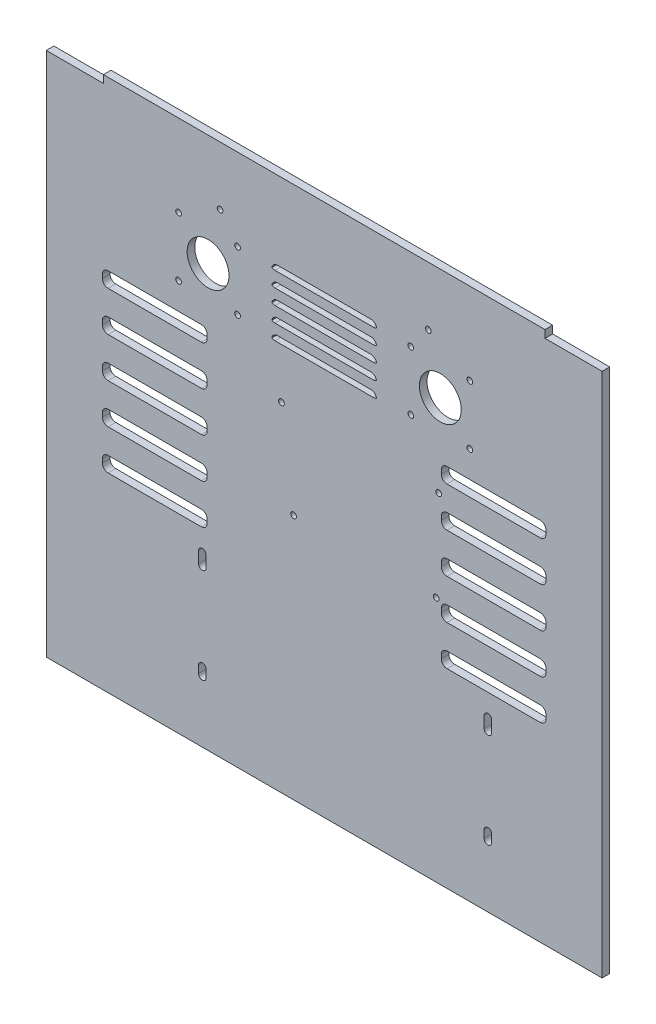
SolidWorks part; units mm, degrees
ref_plane "Front Plane" through (0, 0, 0) normal (0, 0, 1) x (1, 0, 0)
ref_plane "Top Plane" through (0, 0, 0) normal (0, 1, 0) x (1, 0, 0)
ref_plane "Right Plane" through (0, 0, 0) normal (1, 0, 0) x (0, 0, -1)
sketch "Sketch1" plane through (0, 0, 0) normal (0, 0, 1) x (1, 0, 0)
  line L0 (-45.5, 82.5) -> (-76.5, 82.5) construction
  line L1 (146, -123.5) -> (-146, -123.5)
  line L2 (146, -123.5) -> (146, 123.5)
  line L3 (146, 123.5) -> (-146, 123.5)
  line L4 (-146, -123.5) -> (-146, 123.5)
  line L5 (146, -123.5) -> (-146, 123.5) construction
  line L6 (146, 123.5) -> (-146, -123.5) construction
  line L7 (-45.5, 82.5) -> (-45.5, 113.5) construction
  line L8 (-45.5, 113.5) -> (-76.5, 113.5) construction
  line L9 (-76.5, 82.5) -> (-76.5, 113.5) construction
  line L10 (-45.5, 82.5) -> (-76.5, 113.5) construction
  line L11 (-45.5, 113.5) -> (-76.5, 82.5) construction
  line L12 (0, 123.5) -> (0, -133.2191) construction
  line L13 (45.5, 113.5) -> (76.5, 82.5) construction
  line L14 (45.5, 82.5) -> (76.5, 113.5) construction
  line L15 (76.5, 82.5) -> (76.5, 113.5) construction
  line L16 (45.5, 113.5) -> (76.5, 113.5) construction
  line L17 (45.5, 82.5) -> (45.5, 113.5) construction
  line L18 (45.5, 82.5) -> (76.5, 82.5) construction
  line L19 (-175.5662, 125.75) -> (218.0802, 125.75) construction
  line L20 (-146, 123.5) -> (146, 123.5)
  line L21 (-146, 123.5) -> (-146, 156.5)
  line L22 (-146, 156.5) -> (146, 156.5)
  line L23 (146, 123.5) -> (146, 156.5)
  line L24 (0, 156.5) -> (0, 123.5) construction
  line L25 (-146, 140) -> (146, 140) construction
  line L26 (146, 154.5) -> (116, 154.5) construction
  line L27 (-146, 156.5) -> (-116, 156.5)
  line L28 (-146, 156.5) -> (-146, 152.5)
  line L29 (-146, 152.5) -> (-116, 152.5)
  line L30 (-116, 156.5) -> (-116, 152.5)
  line L31 (-131, 152.5) -> (-131, 156.5) construction
  line L32 (-146, 154.5) -> (-116, 154.5) construction
  line L33 (131, 152.5) -> (131, 156.5) construction
  line L34 (116, 156.5) -> (116, 152.5)
  line L35 (146, 152.5) -> (116, 152.5)
  line L36 (146, 156.5) -> (146, 152.5)
  line L37 (146, 156.5) -> (116, 156.5)
  line L38 (-64, -41) -> (-64, -35.0783) construction
  line L39 (-66, -41) -> (-66, -35.0783)
  line L40 (-62, -41) -> (-62, -35.0783)
  line L41 (-64, -91) -> (-64, -87.0783) construction
  line L42 (-66, -91) -> (-66, -87.0783)
  line L43 (-62, -91) -> (-62, -87.0783)
  line L44 (86, -41) -> (86, -35.0783) construction
  line L45 (84, -41) -> (84, -35.0783)
  line L46 (88, -41) -> (88, -35.0783)
  line L47 (86, -91) -> (86, -87.0783) construction
  line L48 (84, -91) -> (84, -87.0783)
  line L49 (88, -91) -> (88, -87.0783)
  line L50 (-116.5, 64.5) -> (-61.5, 64.5) construction
  line L51 (113.5, 68.5) -> (64.5, 68.5)
  line L52 (116.5, 65.5) -> (116.5, 63.5)
  line L53 (113.5, 60.5) -> (64.5, 60.5)
  line L54 (61.5, 65.5) -> (61.5, 63.5)
  line L55 (89, 60.5) -> (89, 68.5) construction
  line L56 (116.5, 64.5) -> (61.5, 64.5) construction
  line L57 (-89, 60.5) -> (-89, 68.5) construction
  line L58 (-61.5, 65.5) -> (-61.5, 63.5)
  line L59 (-113.5, 60.5) -> (-64.5, 60.5)
  line L60 (-116.5, 65.5) -> (-116.5, 63.5)
  line L61 (-113.5, 68.5) -> (-64.5, 68.5)
  line L62 (113.5, 47.5) -> (64.5, 47.5)
  line L63 (116.5, 44.5) -> (116.5, 42.5)
  line L64 (113.5, 39.5) -> (64.5, 39.5)
  line L65 (61.5, 44.5) -> (61.5, 42.5)
  line L66 (-61.5, 44.5) -> (-61.5, 42.5)
  line L67 (-113.5, 39.5) -> (-64.5, 39.5)
  line L68 (-116.5, 44.5) -> (-116.5, 42.5)
  line L69 (-113.5, 47.5) -> (-64.5, 47.5)
  line L70 (-116.5, 43.5) -> (-61.5, 43.5) construction
  line L71 (89, 39.5) -> (89, 47.5) construction
  line L72 (116.5, 43.5) -> (61.5, 43.5) construction
  line L73 (-89, 39.5) -> (-89, 47.5) construction
  line L74 (113.5, 26.5) -> (64.5, 26.5)
  line L75 (116.5, 23.5) -> (116.5, 21.5)
  line L76 (113.5, 18.5) -> (64.5, 18.5)
  line L77 (61.5, 23.5) -> (61.5, 21.5)
  line L78 (-61.5, 23.5) -> (-61.5, 21.5)
  line L79 (-113.5, 18.5) -> (-64.5, 18.5)
  line L80 (-116.5, 23.5) -> (-116.5, 21.5)
  line L81 (-113.5, 26.5) -> (-64.5, 26.5)
  line L82 (-116.5, 22.5) -> (-61.5, 22.5) construction
  line L83 (89, 18.5) -> (89, 26.5) construction
  line L84 (116.5, 22.5) -> (61.5, 22.5) construction
  line L85 (-89, 18.5) -> (-89, 26.5) construction
  line L86 (113.5, 5.5) -> (64.5, 5.5)
  line L87 (116.5, 2.5) -> (116.5, 0.5)
  line L88 (113.5, -2.5) -> (64.5, -2.5)
  line L89 (61.5, 2.5) -> (61.5, 0.5)
  line L90 (-61.5, 2.5) -> (-61.5, 0.5)
  line L91 (-113.5, -2.5) -> (-64.5, -2.5)
  line L92 (-116.5, 2.5) -> (-116.5, 0.5)
  line L93 (-113.5, 5.5) -> (-64.5, 5.5)
  line L94 (-116.5, 1.5) -> (-61.5, 1.5) construction
  line L95 (89, -2.5) -> (89, 5.5) construction
  line L96 (116.5, 1.5) -> (61.5, 1.5) construction
  line L97 (-89, -2.5) -> (-89, 5.5) construction
  line L98 (113.5, -15.5) -> (64.5, -15.5)
  line L99 (116.5, -18.5) -> (116.5, -20.5)
  line L100 (113.5, -23.5) -> (64.5, -23.5)
  line L101 (61.5, -18.5) -> (61.5, -20.5)
  line L102 (-61.5, -18.5) -> (-61.5, -20.5)
  line L103 (-113.5, -23.5) -> (-64.5, -23.5)
  line L104 (-116.5, -18.5) -> (-116.5, -20.5)
  line L105 (-113.5, -15.5) -> (-64.5, -15.5)
  line L106 (-116.5, -19.5) -> (-61.5, -19.5) construction
  line L107 (89, -23.5) -> (89, -15.5) construction
  line L108 (116.5, -19.5) -> (61.5, -19.5) construction
  line L109 (-89, -23.5) -> (-89, -15.5) construction
  line L110 (-24.542, 107.5) -> (24.542, 107.5)
  line L111 (-24.542, 115.5) -> (24.542, 115.5)
  line L112 (-25.8417, 104.5) -> (25.8417, 104.5)
  line L113 (-25.8417, 112.5) -> (25.8417, 112.5)
  line L114 (0, 104.5) -> (0, 107.5) construction
  line L115 (0, 112.5) -> (0, 115.5) construction
  line L116 (-27.5, 113) -> (27.5, 113) construction
  line L117 (-27.5, 105) -> (27.5, 105) construction
  line L118 (-24.542, 99.5) -> (24.542, 99.5)
  line L119 (-25.8417, 96.5) -> (25.8417, 96.5)
  line L120 (0, 96.5) -> (0, 99.5) construction
  line L121 (-27.5, 97) -> (27.5, 97) construction
  line L122 (-24.542, 91.5) -> (24.542, 91.5)
  line L123 (-25.8417, 88.5) -> (25.8417, 88.5)
  line L124 (0, 88.5) -> (0, 91.5) construction
  line L125 (-27.5, 89) -> (27.5, 89) construction
  line L126 (-24.542, 83.5) -> (24.542, 83.5)
  line L127 (-25.8417, 80.5) -> (25.8417, 80.5)
  line L128 (0, 80.5) -> (0, 83.5) construction
  line L129 (-27.5, 81) -> (27.5, 81) construction
  circle A0 centre (-76.5, 113.5) radius 1.5
  circle A1 centre (-45.5, 113.5) radius 1.5
  circle A2 centre (76.5, 82.5) radius 1.5
  circle A3 centre (-61, 98) radius 11
  circle A4 centre (-45.5, 82.5) radius 1.5
  circle A5 centre (-76.5, 82.5) radius 1.5
  circle A6 centre (45.5, 82.5) radius 1.5
  circle A7 centre (61, 98) radius 11
  circle A8 centre (45.5, 113.5) radius 1.5
  circle A9 centre (76.5, 113.5) radius 1.5
  circle A10 centre (86, -41) radius 2 construction
  circle A11 centre (86, -91) radius 2 construction
  circle A12 centre (-64, -41) radius 2 construction
  circle A13 centre (-64, -91) radius 2 construction
  circle A14 centre (60.1213, 54.1951) radius 1.5
  circle A15 centre (-54.7, 125.75) radius 1.5
  circle A16 centre (-16.0787, 5.9351) radius 1.5
  circle A17 centre (58.8513, 5.9351) radius 1.5
  circle A18 centre (-22.4287, 54.1951) radius 1.5
  circle A19 centre (54.7, 125.75) radius 1.5
  arc A20 (-66, -41) -> (-62, -41) centre (-64, -41) ccw
  arc A21 (-62, -35.0783) -> (-66, -35.0783) centre (-64, -35.0783) ccw
  arc A22 (84, -41) -> (88, -41) centre (86, -41) ccw
  arc A23 (-66, -91) -> (-62, -91) centre (-64, -91) ccw
  arc A24 (-62, -87.0783) -> (-66, -87.0783) centre (-64, -87.0783) ccw
  arc A25 (88, -35.0783) -> (84, -35.0783) centre (86, -35.0783) ccw
  arc A26 (84, -91) -> (88, -91) centre (86, -91) ccw
  arc A27 (88, -87.0783) -> (84, -87.0783) centre (86, -87.0783) ccw
  arc A28 (64.5, 68.5) -> (61.5, 65.5) centre (64.5, 65.5) ccw
  arc A29 (64.5, 60.5) -> (61.5, 63.5) centre (64.5, 63.5) cw
  arc A30 (116.5, 63.5) -> (113.5, 60.5) centre (113.5, 63.5) cw
  arc A31 (113.5, 68.5) -> (116.5, 65.5) centre (113.5, 65.5) cw
  arc A32 (-113.5, 68.5) -> (-116.5, 65.5) centre (-113.5, 65.5) ccw
  arc A33 (-116.5, 63.5) -> (-113.5, 60.5) centre (-113.5, 63.5) ccw
  arc A34 (-64.5, 60.5) -> (-61.5, 63.5) centre (-64.5, 63.5) ccw
  arc A35 (-64.5, 68.5) -> (-61.5, 65.5) centre (-64.5, 65.5) cw
  arc A36 (64.5, 47.5) -> (61.5, 44.5) centre (64.5, 44.5) ccw
  arc A37 (64.5, 39.5) -> (61.5, 42.5) centre (64.5, 42.5) cw
  arc A38 (116.5, 42.5) -> (113.5, 39.5) centre (113.5, 42.5) cw
  arc A39 (113.5, 47.5) -> (116.5, 44.5) centre (113.5, 44.5) cw
  arc A40 (-113.5, 47.5) -> (-116.5, 44.5) centre (-113.5, 44.5) ccw
  arc A41 (-116.5, 42.5) -> (-113.5, 39.5) centre (-113.5, 42.5) ccw
  arc A42 (-64.5, 39.5) -> (-61.5, 42.5) centre (-64.5, 42.5) ccw
  arc A43 (-64.5, 47.5) -> (-61.5, 44.5) centre (-64.5, 44.5) cw
  arc A44 (64.5, 26.5) -> (61.5, 23.5) centre (64.5, 23.5) ccw
  arc A45 (64.5, 18.5) -> (61.5, 21.5) centre (64.5, 21.5) cw
  arc A46 (116.5, 21.5) -> (113.5, 18.5) centre (113.5, 21.5) cw
  arc A47 (113.5, 26.5) -> (116.5, 23.5) centre (113.5, 23.5) cw
  arc A48 (-113.5, 26.5) -> (-116.5, 23.5) centre (-113.5, 23.5) ccw
  arc A49 (-116.5, 21.5) -> (-113.5, 18.5) centre (-113.5, 21.5) ccw
  arc A50 (-64.5, 18.5) -> (-61.5, 21.5) centre (-64.5, 21.5) ccw
  arc A51 (-64.5, 26.5) -> (-61.5, 23.5) centre (-64.5, 23.5) cw
  arc A52 (64.5, 5.5) -> (61.5, 2.5) centre (64.5, 2.5) ccw
  arc A53 (64.5, -2.5) -> (61.5, 0.5) centre (64.5, 0.5) cw
  arc A54 (116.5, 0.5) -> (113.5, -2.5) centre (113.5, 0.5) cw
  arc A55 (113.5, 5.5) -> (116.5, 2.5) centre (113.5, 2.5) cw
  arc A56 (-113.5, 5.5) -> (-116.5, 2.5) centre (-113.5, 2.5) ccw
  arc A57 (-116.5, 0.5) -> (-113.5, -2.5) centre (-113.5, 0.5) ccw
  arc A58 (-64.5, -2.5) -> (-61.5, 0.5) centre (-64.5, 0.5) ccw
  arc A59 (-64.5, 5.5) -> (-61.5, 2.5) centre (-64.5, 2.5) cw
  arc A60 (64.5, -15.5) -> (61.5, -18.5) centre (64.5, -18.5) ccw
  arc A61 (64.5, -23.5) -> (61.5, -20.5) centre (64.5, -20.5) cw
  arc A62 (116.5, -20.5) -> (113.5, -23.5) centre (113.5, -20.5) cw
  arc A63 (113.5, -15.5) -> (116.5, -18.5) centre (113.5, -18.5) cw
  arc A64 (-113.5, -15.5) -> (-116.5, -18.5) centre (-113.5, -18.5) ccw
  arc A65 (-116.5, -20.5) -> (-113.5, -23.5) centre (-113.5, -20.5) ccw
  arc A66 (-64.5, -23.5) -> (-61.5, -20.5) centre (-64.5, -20.5) ccw
  arc A67 (-64.5, -15.5) -> (-61.5, -18.5) centre (-64.5, -18.5) cw
  arc A68 (25.8417, 112.5) -> (27.5, 113) centre (25.8417, 115.5) ccw
  arc A69 (-27.5, 113) -> (-25.8417, 112.5) centre (-25.8417, 115.5) ccw
  arc A70 (-24.542, 115.5) -> (-27.5, 113) centre (-24.542, 112.5) ccw
  arc A71 (24.542, 115.5) -> (27.5, 113) centre (24.542, 112.5) cw
  arc A72 (25.8417, 104.5) -> (27.5, 105) centre (25.8417, 107.5) ccw
  arc A73 (-27.5, 105) -> (-25.8417, 104.5) centre (-25.8417, 107.5) ccw
  arc A74 (-24.542, 107.5) -> (-27.5, 105) centre (-24.542, 104.5) ccw
  arc A75 (24.542, 107.5) -> (27.5, 105) centre (24.542, 104.5) cw
  arc A76 (25.8417, 96.5) -> (27.5, 97) centre (25.8417, 99.5) ccw
  arc A77 (-27.5, 97) -> (-25.8417, 96.5) centre (-25.8417, 99.5) ccw
  arc A78 (-24.542, 99.5) -> (-27.5, 97) centre (-24.542, 96.5) ccw
  arc A79 (24.542, 99.5) -> (27.5, 97) centre (24.542, 96.5) cw
  arc A80 (25.8417, 88.5) -> (27.5, 89) centre (25.8417, 91.5) ccw
  arc A81 (-27.5, 89) -> (-25.8417, 88.5) centre (-25.8417, 91.5) ccw
  arc A82 (-24.542, 91.5) -> (-27.5, 89) centre (-24.542, 88.5) ccw
  arc A83 (24.542, 91.5) -> (27.5, 89) centre (24.542, 88.5) cw
  arc A84 (25.8417, 80.5) -> (27.5, 81) centre (25.8417, 83.5) ccw
  arc A85 (-27.5, 81) -> (-25.8417, 80.5) centre (-25.8417, 83.5) ccw
  arc A86 (-24.542, 83.5) -> (-27.5, 81) centre (-24.542, 80.5) ccw
  arc A87 (24.542, 83.5) -> (27.5, 81) centre (24.542, 80.5) cw
  point P0 (0, 0)
  point P63 (131, 154.5)
  point P65 (-64, -38.0392)
  point P73 (-64, -89.0392)
  point P79 (86, -38.0392)
  point P86 (86, -89.0392)
  point P119 (-89, 64.5)
  point P132 (-131, 154.5)
  point P154 (-89, 43.5)
  point P159 (89, 43.5)
  point P164 (89, 64.5)
  point P193 (-89, 22.5)
  point P198 (89, 22.5)
  point P227 (-89, 1.5)
  point P232 (89, 1.5)
  point P261 (-89, -19.5)
  point P266 (89, -19.5)
  point P274 (0, 140)
  point P293 (0, 105)
  point P306 (0, 97)
  point P319 (0, 89)
  point P332 (0, 81)
  point P381 (0, 113)
  dimension "D3" = 22
  dimension "D5" = 3
  dimension "D6" = 85
  dimension "D8" = 3
  dimension "D9" = 3
  dimension "D10" = 3
  dimension "D11" = 2
  dimension "D12" = 2
  dimension "D13" = 2
  dimension "D14" = 2
  dimension "D19" = 3
  dimension "D20" = 3
  dimension "D21" = 3
  dimension "D22" = 3
  dimension "D31" = 3
  dimension "D35" = 2
  dimension "D38" = 3
  dimension "D44" = 3
  dimension "D1" = 292
  dimension "D2" = 247
  dimension "D4" = 31
  dimension "D7" = 10
  dimension "D15" = 82
  dimension "D16" = 150
  dimension "D17" = 50
  dimension "D18" = 32.5
  dimension "D23" = 82.55
  dimension "D24" = 48.26
  dimension "D25" = 74.93
  dimension "D26" = 48.26
  dimension "D27" = 69.3049
  dimension "D28" = 85.8787
  dimension "D29" = 33
  dimension "D30" = 2.25
  dimension "D32" = 54.7
  dimension "D33" = 30
  dimension "D34" = 4
  dimension "D36" = 55
  dimension "D37" = 8
  dimension "D39" = 89
  dimension "D40" = 55
  dimension "D42" = 55
  dimension "D43" = 3
  dimension "D45" = 8
  dimension "D41" = 5
  dimension "D46" = 5
extrude "Boss-Extrude1" add sketch "Sketch1" along normal blind 4 contours L4 L1 L2 L3 A18 A17 A16 A14 A13 A12 A11 A10 A8 A6 A5 A4 A3 A0 A1 A2 A7 A9 | L3 L23 L22 L21 region at (-0.0301, -3.7739, 0) region at (0, 139.6505, 0)
